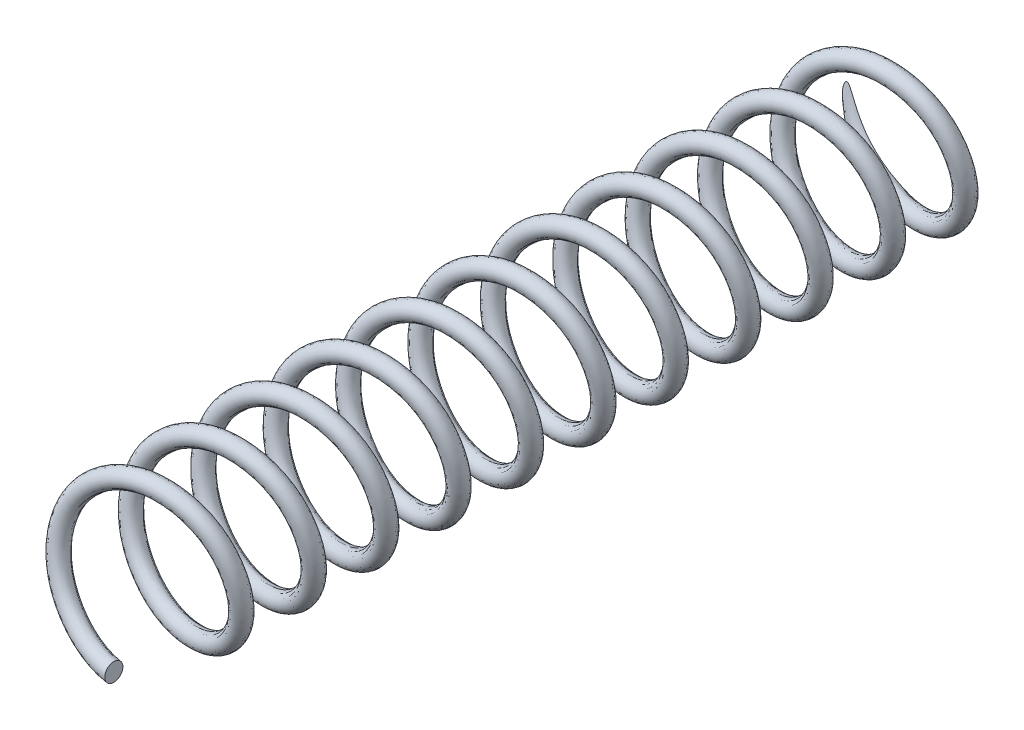
SolidWorks part; units mm, degrees
note: '?' marks a value the reader was unsure of.
ref_plane "Front Plane" through (0, 0, 0) normal (0, 0, 1) x (1, 0, 0)
ref_plane "Top Plane" through (0, 0, 0) normal (0, 1, 0) x (1, 0, 0)
ref_plane "Right Plane" through (0, 0, 0) normal (1, 0, 0) x (0, 0, -1)
sketch "Sketch4" plane through (0, 0, 0) normal (0, 0, 1) x (1, 0, 0)
  circle A0 centre (0, 0) radius 1.0135
curve "Helix/Spiral2" pitch 1.016 height 50.8 turns 50
sketch "Sketch5" plane through (0, 0, 0) normal (1, 0, 0) x (0, 0, -1)
  circle A0 centre (0, -1.0145) radius 0.127
sweep "Sweep1" add profiles "Sketch5" path "Helix/Spiral2"
sketch "Sketch16" plane through (0, 0, 0) normal (1, 0, 0) x (0, 0, -1)
  line L0 (-0.127, -1.0145) -> (-0.127, 4.7526) construction
  line L1 (-0.127, 4.7526) -> (11.303, 4.7526) construction
  line L3 (11.303, 4.7526) -> (55.016, 4.7526)
  line L4 (11.303, 4.7526) -> (11.303, -6.6649)
  line L5 (11.303, -6.6649) -> (55.016, -6.6649)
  line L6 (55.016, 4.7526) -> (55.016, -6.6649)
  circle A0 centre (0, -1.0145) radius 0.127 construction
extrude "Cut-Extrude1" cut sketch "Sketch16" against normal mid plane 2.54
ref_axis "Axis2" through (0, 0, 0.9822) along (0, 0, -1)?
ref_axis "Axis1" through (0, 0, 2.6734) along (0, 0, -1)?
